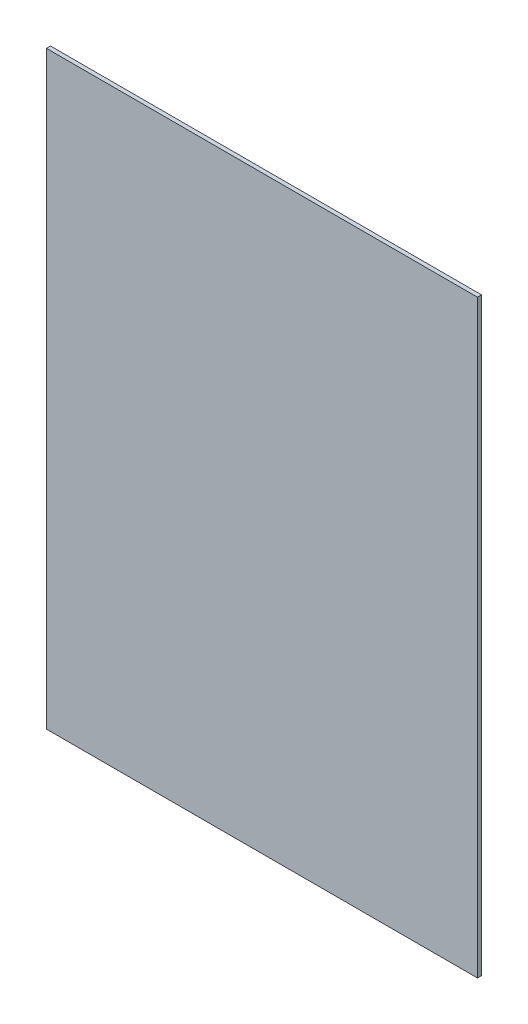
SolidWorks part; units mm, degrees
material "201 Annealed Stainless Steel (SS)"
ref_plane "Front Plane" through (0, 0, 0) normal (0, 0, 1) x (1, 0, 0)
ref_plane "Top Plane" through (0, 0, 0) normal (0, 1, 0) x (1, 0, 0)
ref_plane "Right Plane" through (0, 0, 0) normal (1, 0, 0) x (0, 0, -1)
sketch "Sketch1" plane through (0, 0, 0) normal (0, 0, 1) x (1, 0, 0)
  line L1 (-106, -145) -> (106, -145)
  line L2 (-106, -145) -> (-106, 145)
  line L3 (-106, 145) -> (106, 145)
  line L4 (106, -145) -> (106, 145)
  line L5 (-106, -145) -> (106, 145) construction
  line L6 (-106, 145) -> (106, -145) construction
  point P0 (0, 0)
  dimension "D1" = 212
  dimension "D2" = 290
extrude "Boss-Extrude1" add sketch "Sketch1" along normal blind 2
sketch "Sketch2" [suppressed] plane through (0, 0, 0) normal (0, 0, -1) x (-1, 0, 0)
  line L0 (61, 145) -> (61, -145) construction
  line L1 (-61, 314.7216) -> (-204.3993, 314.7216)
  line L2 (-61, 314.7216) -> (-61, -251.9618)
  line L3 (-61, -251.9618) -> (-204.3993, -251.9618)
  line L4 (-204.3993, 314.7216) -> (-204.3993, -251.9618)
  line L6 (61, 279.3211) -> (244.4765, 279.3211)
  line L7 (61, 279.3211) -> (61, -295.1839)
  line L8 (61, -295.1839) -> (244.4765, -295.1839)
  line L9 (244.4765, 279.3211) -> (244.4765, -295.1839)
  line L10 (-61, -145) -> (-61, 145) construction
  dimension "D1" = 122
extrude "Cut-Extrude1" [suppressed] cut sketch "Sketch2" against normal through all
sketch "Sketch3" [suppressed] plane through (49, 0, 0) normal (1, 0, 0) x (0, 0, -1)
  circle A0 centre (-6.722, 55.3681) radius 5.3835
surface "Surface-Extrude1" [suppressed] sketch "Sketch3"
sketch "Sketch4" [suppressed] plane through (-49, 0, 0) normal (-1, 0, 0) x (0, 0, 1)
  line L1 (2, 80) -> (0, 80) construction
  line L2 (0, -80) -> (0, 80) construction
  point P0 (7.5, 76)
  dimension "D1" = 4
  dimension "D2" = 7.5
ref_axis "Axis1" [suppressed] through (-49, 76, 7.5) along (1, 0, 0)
sketch "Sketch5" [suppressed] plane through (0, 0, 0) normal (0, 0, -1) x (-1, 0, 0)
  line L0 (49, 80) -> (49, -80) construction
  line L1 (-49, 80) -> (49, 80)
  line L2 (-49, 80) -> (-49, 60.2594)
  line L3 (-49, 60.2594) -> (49, 60.2594)
  line L4 (49, 80) -> (49, 60.2594)
extrude "Cut-Extrude2" [suppressed] cut sketch "Sketch5" against normal blind 3
sketch "Sketch6" [suppressed] plane through (0, 0, 2) normal (0, 0, 1) x (1, 0, 0)
  line L0 (0, 0) -> (103.2002, 0) construction
  line L1 (-40, 80) -> (-40, 108.3319) construction
  line L2 (-40, 80) -> (-27.987, 80) construction
  line L3 (0, 0) -> (0, 138.3235) construction
  line L4 (40, 80) -> (27.987, 80) construction
  line L5 (40, 80) -> (40, 108.3319) construction
  line L6 (40, -80) -> (40, -108.3319) construction
  line L7 (40, -80) -> (27.987, -80) construction
  line L8 (-40, -80) -> (-27.987, -80) construction
  line L9 (-40, -80) -> (-40, -108.3319) construction
  circle A0 centre (-40, 80) radius 4.5
  circle A2 centre (-45.8, 85.8) radius 1.95
  circle A3 centre (-45.8, 74.2) radius 1.95
  circle A4 centre (-34.2, 74.2) radius 1.95
  circle A5 centre (-34.2, 85.8) radius 1.95
  circle A6 centre (34.2, 85.8) radius 1.95
  circle A7 centre (34.2, 74.2) radius 1.95
  circle A8 centre (45.8, 74.2) radius 1.95
  circle A9 centre (45.8, 85.8) radius 1.95
  circle A10 centre (40, 80) radius 4.5
  circle A11 centre (40, -80) radius 4.5
  circle A12 centre (45.8, -85.8) radius 1.95
  circle A13 centre (45.8, -74.2) radius 1.95
  circle A14 centre (34.2, -74.2) radius 1.95
  circle A15 centre (34.2, -85.8) radius 1.95
  circle A16 centre (-34.2, -85.8) radius 1.95
  circle A17 centre (-34.2, -74.2) radius 1.95
  circle A18 centre (-45.8, -74.2) radius 1.95
  circle A19 centre (-45.8, -85.8) radius 1.95
  circle A20 centre (-40, -80) radius 4.5
  circle A21 centre (-40, 80) radius 5.1 construction
  dimension "D1" = 9
  dimension "D3" = 3.9
extrude "Leandut_holes" [suppressed] cut sketch "Sketch6" against normal through all
chamfer "Chamfer1" [suppressed] distance 5 angle 45
sketch "Sketch7" plane through (0, 0, 2) normal (0, 0, 1) x (1, 0, 0)
  line L0 (106, 145) -> (-106, 145) construction
  line L1 (-56, -125) -> (56, -125)
  line L2 (-56, -125) -> (-56, 125)
  line L3 (-56, 125) -> (56, 125)
  line L4 (56, -125) -> (56, 125)
  line L5 (-56, -125) -> (56, 125) construction
  line L6 (-56, 125) -> (56, -125) construction
  line L7 (-106, 145) -> (-106, -145) construction
  point P0 (0, 0)
  dimension "D1" = 20
  dimension "D2" = 50
  dimension "D3" = 112
extrude "Plunger-Window" [suppressed] cut sketch "Sketch7" against normal through all
